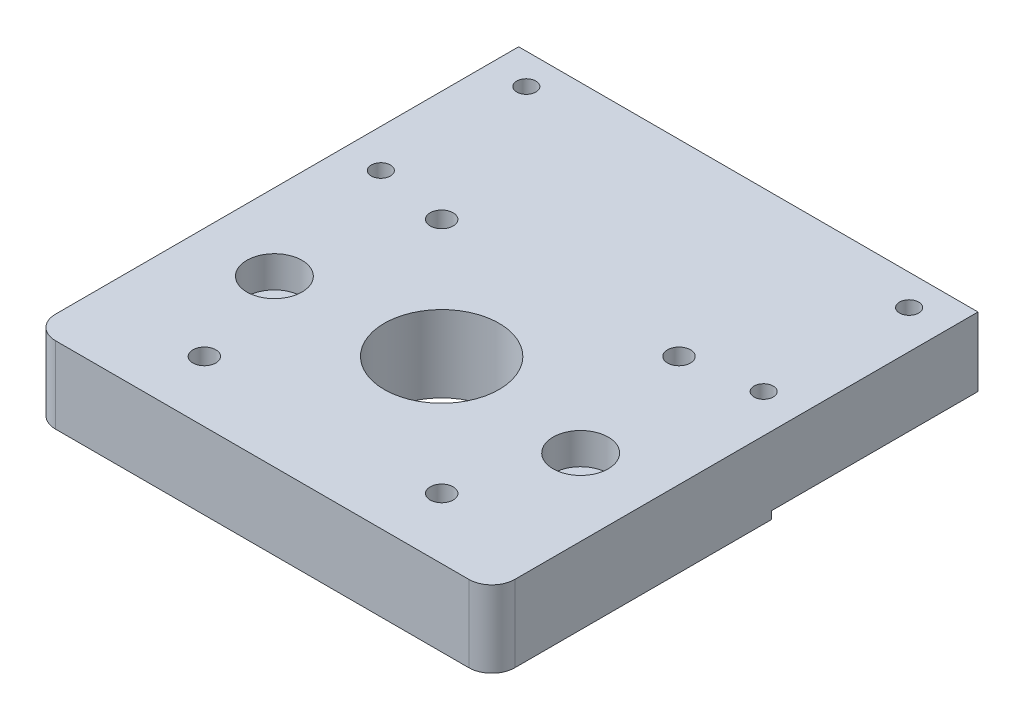
SolidWorks part; units mm, degrees
ref_plane "前视基准面" through (0, 0, 0) normal (0, 0, 1) x (1, 0, 0)
ref_plane "上视基准面" through (0, 0, 0) normal (0, 1, 0) x (1, 0, 0)
ref_plane "右视基准面" through (0, 0, 0) normal (1, 0, 0) x (0, 0, -1)
sketch "草图1" plane through (0, 0, 0) normal (0, 1, 0) x (1, 0, 0)
  line L1 (-30, 31.75) -> (30, 31.75)
  line L2 (-30, 31.75) -> (-30, -31.75)
  line L3 (-30, -31.75) -> (30, -31.75)
  line L4 (30, 31.75) -> (30, -31.75)
  line L5 (-30, 31.75) -> (30, -31.75) construction
  line L6 (-30, -31.75) -> (30, 31.75) construction
  point P0 (0, 0)
  dimension "D1" = 60
  dimension "D2" = 63.5
extrude "凸台-拉伸1" add sketch "草图1" along normal blind 10
fillet "圆角1" radius 3 2 edges at (30, 5, 31.75) (-30, 5, 31.75)
sketch "草图3" plane through (0, 10, 0) normal (0, 1, 0) x (1, 0, 0)
  circle A0 centre (0, -8.3029) radius 7.5
  dimension "D1" = 15
extrude "切除-拉伸2" cut sketch "草图3" against normal through all
sketch "草图4" plane through (0, 0, 0) normal (0, -1, 0) x (1, 0, 0)
  line L1 (20, -4.75) -> (30, -4.75)
  line L2 (20, -7.25) -> (20, -31.75)
  line L3 (20, -31.75) -> (30, -31.75)
  line L4 (30, -4.75) -> (30, -31.75)
  line L5 (-20, -4.75) -> (-30, -4.75)
  line L6 (-20, -7.25) -> (-20, -31.75)
  line L7 (-20, -31.75) -> (-30, -31.75)
  line L8 (-30, -4.75) -> (-30, -31.75)
  arc A1 (-20, -7.25) -> (-20, -4.75) centre (-20, -6) ccw
  arc A4 (20, -4.75) -> (20, -7.25) centre (20, -6) ccw
  point P14 (0, 0)
  dimension "D1" = 2.5
  dimension "D2" = 2.5
extrude "切除-拉伸3" cut sketch "草图4" against normal blind 1
sketch "草图5" plane through (0, 10, 0) normal (0, 1, 0) x (1, 0, 0)
  circle A0 centre (25, 27.75) radius 1.25
  circle A1 centre (25, 8.75) radius 1.25
  circle A2 centre (-25, 27.75) radius 1.25
  circle A3 centre (-25, 8.75) radius 1.25
  dimension "D1" = 2.5
extrude "切除-拉伸4" cut sketch "草图5" against normal through all
sketch "草图7" plane through (0, 0, 0) normal (0, -1, 0) x (1, 0, 0)
  circle A0 centre (-20, 10.15) radius 4
  circle A1 centre (20, 10.15) radius 4
  dimension "D1" = 8
extrude "切除-拉伸6" cut sketch "草图7" against normal blind 1
sketch "草图8" plane through (0, 10, 0) normal (0, 1, 0) x (1, 0, 0)
  circle A0 centre (-20, -10.15) radius 2
  circle A1 centre (20, -10.15) radius 2
  dimension "D1" = 4
extrude "切除-拉伸7" cut sketch "草图8" against normal through all
sketch "草图9" plane through (0, 10, 0) normal (0, 1, 0) x (1, 0, 0)
  circle A0 centre (-20, -10.15) radius 3.6
  circle A1 centre (20, -10.15) radius 3.6
  dimension "D1" = 7.2
extrude "切除-拉伸8" cut sketch "草图9" against normal blind 4.1
sketch "草图10" plane through (0, 10, 0) normal (0, 1, 0) x (1, 0, 0)
  circle A0 centre (-15.5, 7.1971) radius 1.5
  circle A1 centre (15.5, 7.1971) radius 1.5
  circle A2 centre (-15.5, -23.8029) radius 1.5
  circle A3 centre (15.5, -23.8029) radius 1.5
  dimension "D1" = 3
extrude "切除-拉伸9" cut sketch "草图10" against normal through all
sketch "草图11" plane through (0, 0, 0) normal (0, -1, 0) x (1, 0, 0)
  circle A0 centre (-15.5, 23.8029) radius 2.85
  circle A1 centre (15.5, 23.8029) radius 2.85
  circle A2 centre (-15.5, -7.1971) radius 2.85
  circle A3 centre (15.5, -7.1971) radius 2.85
  dimension "D1" = 5.7
extrude "切除-拉伸10" cut sketch "草图11" against normal blind 2.9
